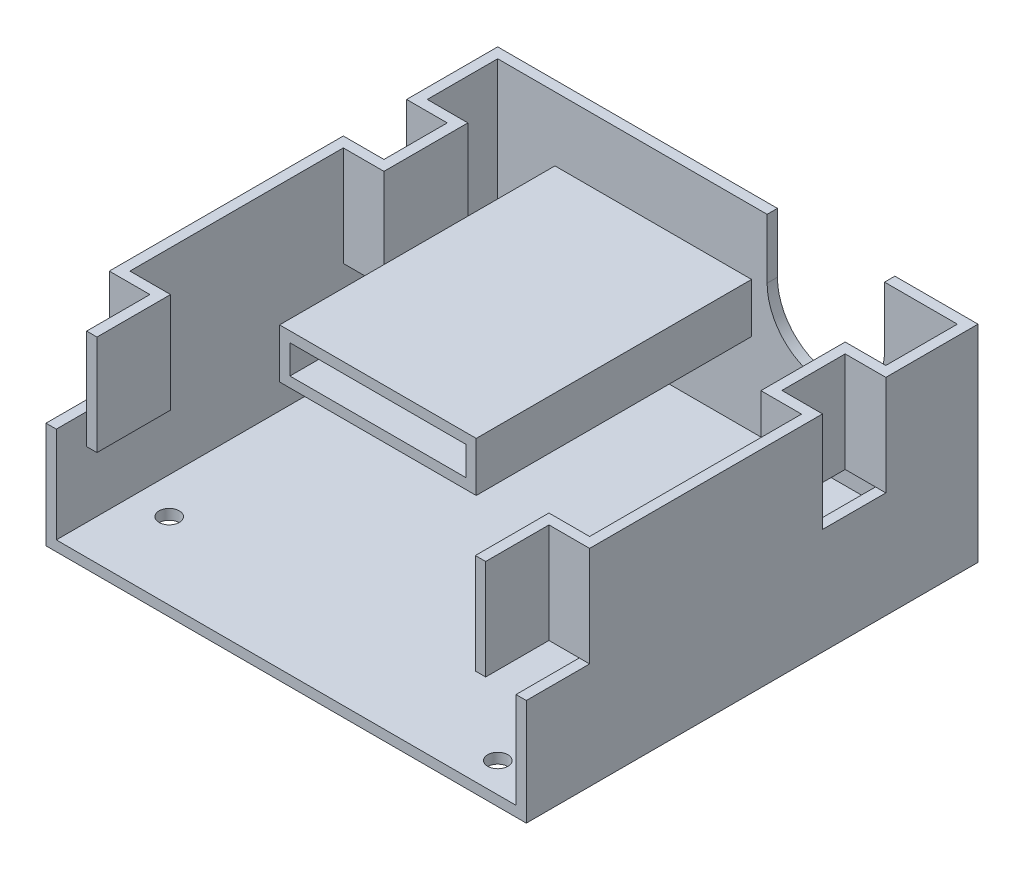
SolidWorks part; units mm, degrees
ref_plane "Front Plane" through (0, 0, 0) normal (0, 0, 1) x (1, 0, 0)
ref_plane "Top Plane" through (0, 0, 0) normal (0, 1, 0) x (1, 0, 0)
ref_plane "Right Plane" through (0, 0, 0) normal (1, 0, 0) x (0, 0, -1)
sketch "Sketch1" plane through (0, 0, 0) normal (0, 1, 0) x (1, 0, 0)
  line L1 (0, 0) -> (89.12, 0)
  line L2 (0, 0) -> (0, 85.57)
  line L3 (0, 85.57) -> (89.12, 85.57)
  line L4 (89.12, 0) -> (89.12, 85.57)
  dimension "D1" = 89.12
  dimension "D2" = 85.57
extrude "Boss-Extrude1" add sketch "Sketch1" along normal blind 2
sketch "Sketch3" plane through (0, 0, 0) normal (0, 0, 1) x (1, 0, 0)
  line L1 (0, 0) -> (-2, 0)
  line L2 (0, 0) -> (0, 30)
  line L3 (0, 30) -> (-2, 30)
  line L4 (-2, 0) -> (-2, 30)
  dimension "D1" = 2
  dimension "D2" = 30
extrude "Boss-Extrude2" add sketch "Sketch3" against normal blind 85.57
sketch "Sketch4" plane through (0, 0, 0) normal (0, 0, 1) x (1, 0, 0)
  line L1 (89.12, 0) -> (91.12, 0)
  line L2 (89.12, 0) -> (89.12, 30)
  line L3 (89.12, 30) -> (91.12, 30)
  line L4 (91.12, 0) -> (91.12, 30)
  dimension "D1" = 30
  dimension "D2" = 2
extrude "Boss-Extrude3" add sketch "Sketch4" against normal blind 85.57
sketch "Sketch5" plane through (0, 0, 0) normal (0, 1, 0) x (1, 0, 0)
  line L1 (-2, 85.57) -> (91.12, 85.57)
  line L2 (-2, 85.57) -> (-2, 87.57)
  line L3 (-2, 87.57) -> (91.12, 87.57)
  line L4 (91.12, 85.57) -> (91.12, 87.57)
  dimension "D1" = 2
extrude "Boss-Extrude4" add sketch "Sketch5" along normal blind 30
sketch "Sketch6" plane through (0, 0, 0) normal (0, 1, 0) x (1, 0, 0)
  line L0 (89.12, 0) -> (89.12, 5.755) construction
  line L1 (89.12, 0) -> (89.12, 85.57) construction
  line L2 (89.12, 5.755) -> (79.835, 5.755) construction
  line L3 (79.835, 5.755) -> (79.835, 0) construction
  line L4 (0, 0) -> (89.12, 0) construction
  circle A0 centre (79.835, 5.755) radius 1.96
  dimension "D3" = 3.92
extrude "Cut-Extrude2" cut sketch "Sketch6" along normal blind 30
sketch "Sketch7" plane through (0, 2, 0) normal (0, 1, 0) x (1, 0, 0)
  line L0 (89.12, 85.57) -> (82.285, 85.57) construction
  line L1 (0, 85.57) -> (89.12, 85.57) construction
  line L2 (82.285, 85.57) -> (82.285, 76.225) construction
  line L3 (82.285, 76.225) -> (89.12, 76.225) construction
  line L4 (89.12, 0) -> (89.12, 85.57) construction
  circle A0 centre (82.285, 76.225) radius 1.96
  dimension "D3" = 3.92
  dimension "D1" = 6.835
extrude "Cut-Extrude3" cut sketch "Sketch7" against normal blind 30
sketch "Sketch8" plane through (0, 0, 0) normal (0, 1, 0) x (1, 0, 0)
  line L0 (0, 85.57) -> (6.985, 85.57) construction
  line L1 (0, 85.57) -> (89.12, 85.57) construction
  line L2 (6.985, 85.57) -> (6.985, 78.28) construction
  line L3 (6.985, 78.28) -> (0, 78.28) construction
  line L4 (0, 85.57) -> (0, 0) construction
  circle A0 centre (6.985, 78.28) radius 1.96
  dimension "D3" = 3.92
  dimension "D1" = 7.29
extrude "Cut-Extrude4" cut sketch "Sketch8" along normal blind 30
sketch "Sketch9" plane through (0, 2, 0) normal (0, 1, 0) x (1, 0, 0)
  line L0 (0, 0) -> (0, 14.85) construction
  line L1 (0, 85.57) -> (0, 0) construction
  line L2 (0, 14.85) -> (7.035, 14.85) construction
  line L3 (7.035, 14.85) -> (7.035, 0) construction
  line L4 (0, 0) -> (89.12, 0) construction
  circle A0 centre (7.035, 14.85) radius 1.96
  dimension "D3" = 3.92
  dimension "D1" = 14.85
extrude "Cut-Extrude5" cut sketch "Sketch9" against normal blind 30
sketch "Sketch10" plane through (89.12, 0, 0) normal (-1, 0, 0) x (0, 0, 1)
  line L0 (0, 2) -> (0, 16.1) construction
  line L1 (0, 30) -> (0, 2) construction
  line L2 (0, 16.1) -> (-32.6241, 16.1) construction
  line L3 (-32.6241, 16.1) -> (-32.6241, 2) construction
  line L4 (0, 2) -> (-85.57, 2) construction
  line L5 (-32.6241, 16.1) -> (-32.6241, 30) construction
  line L6 (-85.57, 30) -> (0, 30) construction
  dimension "D1" = 14.1
sketch "Sketch11" plane through (0, 30, 0) normal (0, 1, 0) x (1, 0, 0)
  line L1 (89.12, 0) -> (83.24, 0)
  line L2 (89.12, 0) -> (89.12, 12.27)
  line L3 (89.12, 12.27) -> (83.24, 12.27)
  line L4 (83.24, 0) -> (83.24, 12.27)
  line L5 (83.24, 0) -> (81.24, 0)
  line L6 (83.24, 0) -> (83.24, 12.27)
  line L7 (83.24, 12.27) -> (81.24, 12.27)
  line L8 (81.24, 0) -> (81.24, 12.27)
  line L9 (81.24, 12.27) -> (89.12, 12.27)
  line L10 (81.24, 12.27) -> (81.24, 14.27)
  line L11 (81.24, 14.27) -> (89.12, 14.27)
  line L12 (89.12, 12.27) -> (89.12, 14.27)
  line M8 (89.12, 85.57) -> (89.12, 0)
  dimension "D1" = 5.88
  dimension "D2" = 12.27
  dimension "D3" = 2
  dimension "D4" = 2
extrude "Boss-Extrude5" add sketch "Sketch11" against normal blind 9.4 contours L11 L10 L7 L3 M8 | L8 L5 L4 L7 region at (82.24, 30, -6.135) region at (85.18, 30, -13.27)
sketch "Sketch12" plane through (0, 30, 0) normal (0, 1, 0) x (1, 0, 0)
  line L1 (89.12, 12.27) -> (91.12, 12.27)
  line L2 (89.12, 12.27) -> (89.12, 0)
  line L3 (89.12, 0) -> (91.12, 0)
  line L4 (91.12, 12.27) -> (91.12, 0)
extrude "Cut-Extrude6" cut sketch "Sketch12" against normal blind 9.4
sketch "Sketch13" plane through (0, 30, 0) normal (0, 1, 0) x (1, 0, 0)
  line L0 (89.12, 85.57) -> (89.12, 57.43) construction
  line L1 (89.12, 85.57) -> (89.12, 14.27) construction
  line L3 (89.12, 57.43) -> (83.24, 57.43)
  line L4 (89.12, 57.43) -> (89.12, 69.7)
  line L5 (89.12, 69.7) -> (83.24, 69.7)
  line L6 (83.24, 57.43) -> (83.24, 69.7)
  line L7 (83.24, 69.7) -> (81.24, 69.7)
  line L8 (83.24, 69.7) -> (83.24, 57.43)
  line L9 (83.24, 57.43) -> (81.24, 57.43)
  line L10 (81.24, 69.7) -> (81.24, 57.43)
  line L11 (81.24, 57.43) -> (89.12, 57.43)
  line L12 (81.24, 57.43) -> (81.24, 55.3598)
  line L13 (81.24, 55.3598) -> (89.12, 55.3598)
  line L14 (89.12, 57.43) -> (89.12, 55.3598)
  line L15 (81.24, 69.7) -> (89.12, 69.7)
  line L16 (81.24, 69.7) -> (81.24, 71.7)
  line L17 (81.24, 71.7) -> (89.12, 71.7)
  line L18 (89.12, 69.7) -> (89.12, 71.7)
  line M25 (89.12, 85.57) -> (89.12, 14.27)
  dimension "D1" = 28.14
  dimension "D2" = 12.27
  dimension "D3" = 5.88
  dimension "D4" = 2
  dimension "D5" = 2.0702
  dimension "D6" = 2
extrude "Boss-Extrude6" add sketch "Sketch13" against normal blind 9.4 contours L17 L16 L7 L5 M25 | L7 L10 L9 L6 | L12 L13 L3 L9 M25 region at (85.18, 30, -56.3949) region at (82.24, 30, -63.565) region at (85.18, 30, -70.7)
sketch "Sketch14" plane through (0, 30, 0) normal (0, 1, 0) x (1, 0, 0)
  line L0 (91.12, 87.57) -> (91.12, 12.27) construction
  line L1 (89.12, 69.7) -> (91.12, 69.7)
  line L2 (89.12, 69.7) -> (89.12, 57.43)
  line L3 (89.12, 57.43) -> (91.12, 57.43)
  line L4 (91.12, 69.7) -> (91.12, 57.43)
extrude "Cut-Extrude7" cut sketch "Sketch14" against normal blind 9.4
sketch "Sketch15" plane through (0, 30, 0) normal (0, 1, 0) x (1, 0, 0)
  line L0 (0, 85.57) -> (0, 57.64) construction
  line L1 (0, 85.57) -> (0, 0) construction
  line L3 (0, 57.64) -> (5.88, 57.64)
  line L4 (0, 57.64) -> (0, 69.91)
  line L5 (0, 69.91) -> (5.88, 69.91)
  line L6 (5.88, 57.64) -> (5.88, 69.91)
  line L7 (5.88, 69.91) -> (7.88, 69.91)
  line L8 (5.88, 69.91) -> (5.88, 57.64)
  line L9 (5.88, 57.64) -> (7.88, 57.64)
  line L10 (7.88, 69.91) -> (7.88, 57.64)
  line L11 (0, 57.64) -> (7.88, 57.64)
  line L12 (0, 57.64) -> (0, 55.64)
  line L13 (0, 55.64) -> (7.88, 55.64)
  line L14 (7.88, 57.64) -> (7.88, 55.64)
  line L15 (0, 69.91) -> (7.88, 69.91)
  line L16 (0, 69.91) -> (0, 71.91)
  line L17 (0, 71.91) -> (7.88, 71.91)
  line L18 (7.88, 69.91) -> (7.88, 71.91)
  line M12 (0, 0) -> (0, 85.57)
  dimension "D1" = 27.93
  dimension "D2" = 5.88
  dimension "D3" = 12.27
  dimension "D4" = 2
  dimension "D5" = 2
  dimension "D6" = 2
extrude "Boss-Extrude7" add sketch "Sketch15" against normal blind 9.4 contours L7 L18 L17 L5 M12 | L10 L7 L6 L9 | L14 L9 L3 L13 M12 region at (3.94, 30, -56.64) region at (6.88, 30, -63.775) region at (3.94, 30, -70.91)
sketch "Sketch16" plane through (0, 30, 0) normal (0, 1, 0) x (1, 0, 0)
  line L0 (-2, 87.57) -> (-2, 0) construction
  line L1 (-2, 69.91) -> (0, 69.91)
  line L2 (-2, 69.91) -> (-2, 57.64)
  line L3 (-2, 57.64) -> (0, 57.64)
  line L4 (0, 69.91) -> (0, 57.64)
extrude "Cut-Extrude8" cut sketch "Sketch16" against normal blind 9.4
sketch "Sketch17" plane through (0, 30, 0) normal (0, 1, 0) x (1, 0, 0)
  line L0 (0, 0) -> (89.12, 0) construction
  line L1 (0, 0) -> (5.88, 0)
  line L2 (0, 0) -> (0, 12.27)
  line L3 (0, 12.27) -> (5.88, 12.27)
  line L4 (5.88, 0) -> (5.88, 12.27)
  line L5 (5.88, 12.27) -> (7.88, 12.27)
  line L6 (5.88, 12.27) -> (5.88, 0)
  line L7 (5.88, 0) -> (7.88, 0)
  line L8 (7.88, 12.27) -> (7.88, 0)
  line L9 (0, 55.64) -> (0, 0) construction
  line L10 (7.88, 12.27) -> (0, 12.27)
  line L11 (7.88, 12.27) -> (7.88, 14.27)
  line L12 (7.88, 14.27) -> (0, 14.27)
  line L13 (0, 12.27) -> (0, 14.27)
  line M13 (0, 0) -> (0, 55.64)
  dimension "D1" = 12.27
  dimension "D2" = 5.88
  dimension "D3" = 2
  dimension "D4" = 2
extrude "Boss-Extrude8" add sketch "Sketch17" against normal blind 9.4 contours L11 L12 L3 L5 M13 | L8 L5 L4 L7 region at (6.88, 30, -6.135) region at (3.94, 30, -13.27)
sketch "Sketch18" plane through (0, 30, 0) normal (0, 1, 0) x (1, 0, 0)
  line L0 (-2, 57.64) -> (-2, 0) construction
  line L1 (0, 0) -> (-2, 0)
  line L2 (0, 0) -> (0, 12.27)
  line L3 (0, 12.27) -> (-2, 12.27)
  line L4 (-2, 0) -> (-2, 12.27)
extrude "Cut-Extrude9" cut sketch "Sketch18" against normal blind 9.4
sketch "Sketch19" plane through (0, 30, 0) normal (0, 1, 0) x (1, 0, 0)
  line L0 (83.24, 0) -> (81.24, 0)
  line L1 (81.24, 0) -> (81.24, 14.27)
  line L2 (81.24, 0) -> (81.24, 14.27) construction
  line L3 (81.24, 14.27) -> (89.12, 14.27)
  line L4 (89.12, 14.27) -> (89.12, 55.3598)
  line L5 (89.12, 55.3598) -> (81.24, 55.3598)
  line L6 (81.24, 55.3598) -> (81.24, 71.7)
  line L7 (81.24, 71.7) -> (89.12, 71.7)
  line L8 (89.12, 71.7) -> (89.12, 85.57)
  line L9 (89.12, 85.57) -> (0, 85.57)
  line L10 (0, 85.57) -> (0, 71.91)
  line L11 (0, 71.91) -> (7.88, 71.91)
  line L12 (7.88, 71.91) -> (7.88, 55.64)
  line L13 (7.88, 55.64) -> (0, 55.64)
  line L14 (0, 55.64) -> (0, 14.27)
  line L15 (0, 14.27) -> (7.88, 14.27)
  line L16 (7.88, 14.27) -> (7.88, 0)
  line L17 (7.88, 0) -> (5.88, 0)
  line L18 (5.88, 0) -> (5.88, 12.27)
  line L19 (5.88, 12.27) -> (-2, 12.27)
  line L20 (-2, 12.27) -> (-2, 57.64)
  line L21 (-2, 57.64) -> (5.88, 57.64)
  line L22 (5.88, 57.64) -> (5.88, 69.91)
  line L23 (5.88, 69.91) -> (-2, 69.91)
  line L24 (-2, 69.91) -> (-2, 87.57)
  line L25 (-2, 87.57) -> (91.12, 87.57)
  line L26 (91.12, 87.57) -> (91.12, 69.7)
  line L27 (91.12, 69.7) -> (83.24, 69.7)
  line L28 (83.24, 69.7) -> (83.24, 57.43)
  line L29 (83.24, 57.43) -> (91.12, 57.43)
  line L30 (91.12, 57.43) -> (91.12, 12.27)
  line L31 (91.12, 12.27) -> (83.24, 12.27)
  line L32 (83.24, 12.27) -> (83.24, 0)
extrude "Boss-Extrude9" add sketch "Sketch19" along normal blind 10
sketch "Sketch20" plane through (0, 2, 0) normal (0, 1, 0) x (1, 0, 0)
  line L0 (0, 85.57) -> (27.1, 85.57) construction
  line L1 (89.12, 85.57) -> (0, 85.57) construction
  line L2 (27.1, 85.57) -> (27.1, 43.02) construction
  line L3 (27.1, 43.02) -> (11.1, 43.02) construction
  line L4 (11.1, 43.02) -> (11.1, 85.57) construction
  line L6 (11.1, 85.57) -> (27.1, 85.57)
  line L7 (11.1, 85.57) -> (11.1, 43.02)
  line L8 (11.1, 43.02) -> (27.1, 43.02)
  line L9 (27.1, 85.57) -> (27.1, 43.02)
  dimension "D1" = 42.55
  dimension "D2" = 27.1
  dimension "D3" = 16
extrude "Boss-Extrude10" add sketch "Sketch20" along normal blind 8.88
sketch "Sketch21" plane through (0, 0, -43.02) normal (0, 0, 1) x (1, 0, 0)
  line L0 (27.1, 10.88) -> (27.1, 2) construction
  line L1 (11.1, 10.88) -> (27.1, 10.88)
  line L2 (11.1, 10.88) -> (11.1, 8.88)
  line L3 (11.1, 8.88) -> (27.1, 8.88)
  line L4 (27.1, 10.88) -> (27.1, 8.88)
  line L6 (11.1, 8.88) -> (27.1, 8.88)
  line L7 (11.1, 8.88) -> (11.1, 2)
  line L8 (11.1, 2) -> (27.1, 2)
  line L9 (27.1, 8.88) -> (27.1, 2)
  line M2 (11.1, 2) -> (27.1, 2)
  line M3 (27.1, 2) -> (27.1, 10.88)
  line M5 (11.1, 10.88) -> (11.1, 2)
  dimension "D1" = 2
extrude "Cut-Extrude10" cut sketch "Sketch21" against normal blind 42.55 contours L3 M5 M2 M3 region at (19.1, 5.44, -43.02)
sketch "Sketch22" plane through (0, 0, -85.57) normal (0, 0, 1) x (1, 0, 0)
  line L0 (11.1, 10.88) -> (11.1, 17.9689) construction
  line L2 (11.1, 17.9689) -> (49.22, 17.9689)
  line L3 (11.1, 17.9689) -> (11.1, 27.5589)
  line L4 (11.1, 27.5589) -> (49.22, 27.5589)
  line L5 (49.22, 17.9689) -> (49.22, 27.5589)
  dimension "D1" = 38.12
  dimension "D2" = 9.59
extrude "Boss-Extrude11" add sketch "Sketch22" along normal blind 53.38
sketch "Sketch23" plane through (0, 0, -32.19) normal (0, 0, 1) x (1, 0, 0)
  line L0 (13.1, 27.5589) -> (13.1, 25.5589) construction
  line L1 (49.22, 27.5589) -> (11.1, 27.5589) construction
  line L2 (13.1, 25.5589) -> (11.1, 25.5589) construction
  line L3 (11.1, 27.5589) -> (11.1, 17.9689) construction
  line L4 (47.22, 17.9689) -> (47.22, 19.9689) construction
  line L5 (11.1, 17.9689) -> (49.22, 17.9689) construction
  line L6 (47.22, 19.9689) -> (49.22, 19.9689) construction
  line L7 (49.22, 17.9689) -> (49.22, 27.5589) construction
  line L9 (13.1, 25.5589) -> (47.22, 25.5589)
  line L10 (13.1, 25.5589) -> (13.1, 19.9689)
  line L11 (13.1, 19.9689) -> (47.22, 19.9689)
  line L12 (47.22, 25.5589) -> (47.22, 19.9689)
  dimension "D1" = 2
  dimension "D2" = 2
  dimension "D3" = 2
  dimension "D4" = 2
extrude "Cut-Extrude11" cut sketch "Sketch23" against normal blind 53.38
sketch "Sketch24" plane through (0, 0, -85.57) normal (0, 0, 1) x (1, 0, 0)
  line L0 (27.1, 8.88) -> (89.12, 9.05) construction
  line L1 (89.12, 16.1) -> (89.12, 2) construction
  line L2 (89.12, 9.05) -> (89.12, 17.05) construction
  line L3 (89.12, 17.05) -> (63.62, 17.05) construction
  line L4 (63.62, 17.05) -> (63.62, 28.435) construction
  circle A0 centre (63.62, 28.435) radius 11.385
  dimension "D4" = 22.77
  dimension "D1" = 8
  dimension "D2" = 25.5
  dimension "D3" = 11.385
extrude "Cut-Extrude12" cut sketch "Sketch24" against normal blind 53.4
sketch "Sketch25" plane through (0, 0, -85.57) normal (0, 0, 1) x (1, 0, 0)
  line L0 (52.235, 28.435) -> (52.235, 40)
  line L1 (0, 40) -> (89.12, 40) construction
  line L2 (52.235, 40) -> (75.005, 40)
  line L3 (75.005, 40) -> (75.005, 28.435)
  line L4 (75.005, 28.435) -> (52.235, 28.435)
  circle A0 centre (63.62, 28.435) radius 11.385 construction
extrude "Cut-Extrude13" cut sketch "Sketch25" against normal blind 53.4
equation "\"tol1\"= 0.1cm"
equation "\"D1@Sketch1\"=8.812cm +\"tol1\""
equation "\"D2@Sketch1\"=8.457cm +\"tol1\""
equation "\"D1@Boss-Extrude2\"=8.457 +\"tol1\""
equation "\"D1@Boss-Extrude3\"=8.457 +\"tol1\""
equation "\"D1@Sketch6\"=0.5255 + \"tol2\""
equation "\"hole\"= 0.392cm"
equation "\"D3@Sketch6\"=\"hole\""
equation "\"tol2\"= \"tol1\" / 2"
equation "\"D2@Sketch6\"=0.8785 + \"tol2\""
equation "\"D2@Sketch9\"=0.6535 + \"tol2\""
equation "\"D3@Sketch9\"=\"hole\""
equation "\"D1@Sketch9\"=1.435 + \"tol2\""
equation "\"D2@Sketch8\"=0.6485 + \"tol2\""
equation "\"D1@Sketch8\"=0.679 + \"tol2\""
equation "\"D3@Sketch8\"=\"hole\""
equation "\"D3@Sketch7\"=\"hole\""
equation "\"D2@Sketch7\"=0.8845 + \"tol2\""
equation "\"D1@Sketch7\"=0.6335 + \"tol2\""
equation "\"heightTol\"= 0.05cm"
equation "\"D1@Sketch10\"=1.36 + \"heightTol\""
equation "\"D2@Sketch20\"=2.61 + \"tol1\""
equation "\"D1@Boss-Extrude10\"=0.588 + \"tol1\" +0.2"
equation "\"batTol\"= 0.05cm"
equation "\"D1@Sketch22\"=3.362+0.4 +\"batTol\""
equation "\"D2@Sketch22\"=0.509+0.4 + \"batTol\""
equation "\"D1@Boss-Extrude11\"=5.288 + \"batTol\""
equation "\"D1@Cut-Extrude11\"=5.288 + \"batTol\""
equation "\"D2@Sketch24\"=2.5 +\"tol2\""
